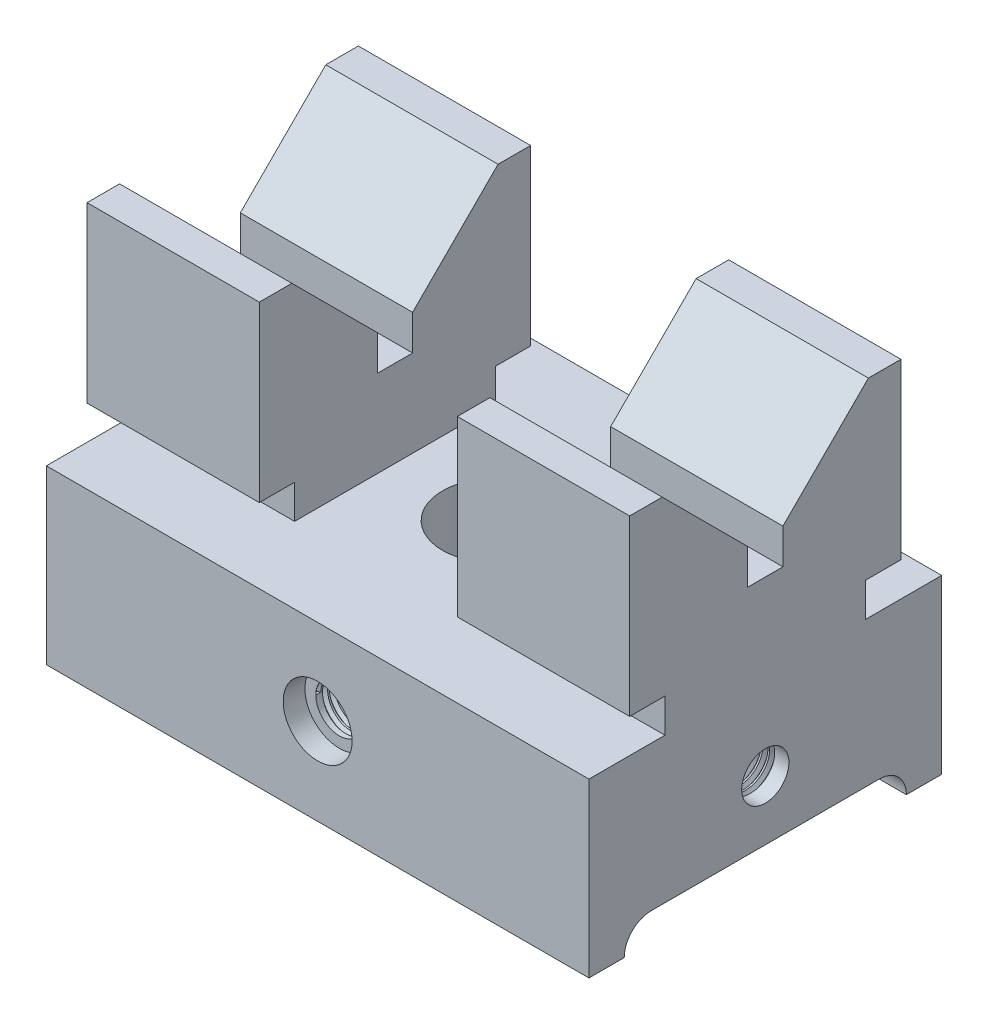
SolidWorks part; units mm, degrees
ref_plane "Front Plane" through (0, 0, 0) normal (0, 0, 1) x (1, 0, 0)
ref_plane "Top Plane" through (0, 0, 0) normal (0, 1, 0) x (1, 0, 0)
ref_plane "Right Plane" through (0, 0, 0) normal (1, 0, 0) x (0, 0, -1)
sketch "Sketch1" plane through (0, 0, 0) normal (1, 0, 0) x (0, 0, -1)
  line L1 (32.5, -35) -> (-32.5, -35)
  line L2 (32.5, -35) -> (32.5, 35)
  line L3 (32.5, 35) -> (-32.5, 35)
  line L4 (-32.5, -35) -> (-32.5, 35)
  line L5 (32.5, -35) -> (-32.5, 35) construction
  line L6 (32.5, 35) -> (-32.5, -35) construction
  point P0 (0, 0)
  dimension "D1" = 65
  dimension "D2" = 70
extrude "Boss-Extrude1" add sketch "Sketch1" along normal mid plane 100
sketch "Sketch3" plane through (50, 0, 0) normal (1, 0, 0) x (0, 0, -1)
  line L0 (0, 35) -> (0, -35) construction
  line L1 (32.5, 35) -> (-32.5, 35) construction
  line L2 (-32.5, -35) -> (32.5, -35) construction
  line L3 (-32.5, -3.25) -> (-18.5, -3.25)
  line L4 (-32.5, 35) -> (-32.5, -35) construction
  line L5 (-18.5, -3.25) -> (-18.5, 3)
  line L6 (-18.5, 3) -> (-25, 3)
  line L7 (-25, 3) -> (-25, 35)
  line L8 (-25, 35) -> (-19, 35)
  line L9 (-19, 35) -> (-3.25, 19.25)
  line L10 (-3.25, 19.25) -> (-3.25, 12.75)
  line L11 (19, 35) -> (3.25, 19.25)
  line L12 (25, 35) -> (19, 35)
  line L13 (25, 3) -> (25, 35)
  line L14 (18.5, 3) -> (25, 3)
  line L15 (18.5, -3.25) -> (18.5, 3)
  line L16 (32.5, -3.25) -> (18.5, -3.25)
  line L17 (-3.25, 12.75) -> (3.25, 12.75)
  line L18 (3.25, 12.75) -> (3.25, 19.25)
  line L19 (32.5, -35) -> (32.5, 35) construction
  line L20 (-26, -35) -> (26, -35)
  line L21 (-26, -35) -> (-26, -30)
  line L22 (-26, -30) -> (26, -30)
  line L23 (26, -35) -> (26, -30)
  point P17 (0, 17.667)
  line M1 (-32.5, 35) -> (-32.5, -35)
  line M3 (32.5, -35) -> (32.5, 35)
  line M4 (32.5, 35) -> (-32.5, 35)
  dimension "D1" = 14
  dimension "D2" = 50
  dimension "D3" = 38
  dimension "D4" = 90
  dimension "D5" = 47.75
  dimension "D6" = 38
  dimension "D7" = 31.75
  dimension "D8" = 6.5
  dimension "D9" = 5
  dimension "D10" = 6.5
  dimension "D11" = 6.5
extrude "Cut-Extrude1" cut sketch "Sketch3" against normal through all contours L16 L13 L14 L15 M3 M4 | L0 L17 L18 L11 M4 | L0 L9 L10 L17 M4 | L6 L7 L3 L5 M4 M1 | L22 L23 L20 L21 region at (50, 27.5863, -5.968) region at (50, 13.8903, -27.8817) region at (50, 13.8903, 27.8817) region at (50, 27.5863, 5.968)
fillet "Fillet1" radius 5 2 edges at (0, -30, 26) (0, -30, -26)
sketch "Sketch4" plane through (50, 0, 0) normal (1, 0, 0) x (0, 0, -1)
  line L0 (-18.5, -3.25) -> (18.5, -3.25)
  line L20 (-32.5, -35) -> (-26, -35)
  line L21 (-21, -30) -> (21, -30)
  line L22 (26, -35) -> (32.5, -35)
  line L23 (32.5, -35) -> (32.5, -3.25)
  line L24 (32.5, -3.25) -> (18.5, -3.25)
  line L25 (18.5, -3.25) -> (18.5, 3)
  line L26 (18.5, 3) -> (25, 3)
  line L27 (25, 3) -> (25, 35)
  line L28 (25, 35) -> (19, 35)
  line L29 (19, 35) -> (3.25, 19.25)
  line L30 (3.25, 19.25) -> (3.25, 12.75)
  line L31 (3.25, 12.75) -> (-3.25, 12.75)
  line L32 (-3.25, 12.75) -> (-3.25, 19.25)
  line L33 (-3.25, 19.25) -> (-19, 35)
  line L34 (-19, 35) -> (-25, 35)
  line L35 (-25, 35) -> (-25, 3)
  line L36 (-25, 3) -> (-18.5, 3)
  line L37 (-18.5, 3) -> (-18.5, -3.25)
  line L38 (-18.5, -3.25) -> (-32.5, -3.25)
  line L39 (-32.5, -3.25) -> (-32.5, -35)
  line L40 (-32.5, -35) -> (-26, -35)
  line L41 (-21, -30) -> (21, -30)
  line L42 (26, -35) -> (32.5, -35)
  line L43 (32.5, -35) -> (32.5, -3.25)
  line L44 (32.5, -3.25) -> (18.5, -3.25)
  line L45 (18.5, -3.25) -> (18.5, 3)
  line L46 (18.5, 3) -> (25, 3)
  line L47 (25, 3) -> (25, 35)
  line L48 (25, 35) -> (19, 35)
  line L49 (19, 35) -> (3.25, 19.25)
  line L50 (3.25, 19.25) -> (3.25, 12.75)
  line L51 (3.25, 12.75) -> (-3.25, 12.75)
  line L52 (-3.25, 12.75) -> (-3.25, 19.25)
  line L53 (-3.25, 19.25) -> (-19, 35)
  line L54 (-19, 35) -> (-25, 35)
  line L55 (-25, 35) -> (-25, 3)
  line L56 (-25, 3) -> (-18.5, 3)
  line L57 (-18.5, 3) -> (-18.5, -3.25)
  line L58 (-18.5, -3.25) -> (-32.5, -3.25)
  line L59 (-32.5, -3.25) -> (-32.5, -35)
  arc A2 (-21, -30) -> (-26, -35) centre (-21, -35) ccw
  arc A3 (26, -35) -> (21, -30) centre (21, -35) ccw
  arc A4 (-21, -30) -> (-26, -35) centre (-21, -35) ccw
  arc A5 (26, -35) -> (21, -30) centre (21, -35) ccw
  line M8 (18.5, -3.25) -> (18.5, 3)
  line M9 (18.5, 3) -> (25, 3)
  line M10 (25, 3) -> (25, 35)
  line M11 (25, 35) -> (19, 35)
  line M12 (19, 35) -> (3.25, 19.25)
  line M13 (3.25, 19.25) -> (3.25, 12.75)
  line M14 (3.25, 12.75) -> (-3.25, 12.75)
  line M15 (-3.25, 12.75) -> (-3.25, 19.25)
  line M16 (-3.25, 19.25) -> (-19, 35)
  line M17 (-19, 35) -> (-25, 35)
  line M18 (-25, 35) -> (-25, 3)
  line M19 (-25, 3) -> (-18.5, 3)
  line M20 (-18.5, 3) -> (-18.5, -3.25)
  dimension "D1" = 0
extrude "Cut-Extrude2" cut sketch "Sketch4" against normal blind 36.5 from offset 31.75 contours L0 M20 M8 M9 M10 M11 M12 M13 M14 M15 M16 M17 M18 M19 region at (50, -0.125, 17.8705) offset against normal yes
sketch "Sketch5" plane through (0, -3.25, 0) normal (0, 1, 0) x (1, 0, 0)
  circle A0 centre (0, 0) radius 9.5
  dimension "D1" = 19
extrude "Cut-Extrude3" cut sketch "Sketch5" against normal through all
hole_wizard "CBORE for M10 Hex Head Machine Screw1" positions "Sketch6" profile "Sketch7" counterbore size "M10" standard "ANSI Metric"
sketch "Sketch6" plane through (0, 0, 32.5) normal (0, 0, 1) x (1, 0, 0)
  line L0 (-50, -3.25) -> (-50, -35) construction
  line L1 (50, -35) -> (-50, -35) construction
  point P0 (0, -19)
  dimension "D1" = 50
  dimension "D2" = 16
sketch "Sketch7" plane through (0, -19, 32.5) normal (1, 0, 0) x (0, -1, 0)
  line L0 (0, 0) -> (0, 22.6137)
  line L1 (0, 22.6137) -> (4.35, 20)
  line L2 (4.35, 20) -> (4.35, 4)
  line L3 (4.35, 4) -> (6.35, 4)
  line L4 (6.35, 4) -> (6.35, 0)
  line L5 (6.35, 0) -> (0, 0)
  line L10 (0, 22.6137) -> (-4.35, 20) construction
  line L11 (0, -6.35) -> (0, 107.95) construction
  dimension "Hole Dia." = 8.7
  dimension "Hole Depth" = 20
  dimension "C'Bore Dia." = 12.7
  dimension "C'Bore Depth" = 4
  dimension "Drill Angle" = 118
thread "Thread1" pitch 1.25 method cut profile "Thread Profile1" start angle 0, offset 0, length 10, pitch 1.25, diameter 8.7
ref_plane "Plane1" through (-4.35, -19, 28.5) normal (0, -1, 0) x (-1, 0, 0)
sketch "Thread Profile1" plane through (-4.35, -19, 28.5) normal (0, -1, 0) x (-1, 0, 0)
  line L0 (0, 0) -> (0, 1.25) construction
  line L1 (0, 0) -> (0.6766, 0.3906)
  line L2 (0.6766, 0.3906) -> (0.6766, 0.5469)
  line L3 (0.6766, 0.5469) -> (0, 0.9375)
  line L4 (0.6766, 0.4687) -> (0, 0.4687) construction
  line L11 (0, 0) -> (0, 0.9375)
  point P2 (0, 0)
  dimension "Pitch" = 1.25
  dimension "Profile_Angle" = 60
  dimension "Profile_Land" = 0.1562
  dimension "Profile_Height" = 0.6766
hole_wizard "Ø8.7 (8.7) Diameter Hole1" positions "Sketch12" profile "Sketch13" hole size "Ø8.7" standard "ANSI Metric"
sketch "Sketch12" plane through (50, 0, 0) normal (1, 0, 0) x (0, 0, -1)
  line L0 (-32.5, -3.25) -> (-32.5, -35) construction
  line L1 (-32.5, -35) -> (-26, -35) construction
  point P0 (0, -19)
  dimension "D1" = 32.5
  dimension "D2" = 16
sketch "Sketch13" plane through (50, -19, 0) normal (0, 1, 0) x (0, 0, -1)
  line L0 (0, 0) -> (0, 18.6137)
  line L1 (0, 18.6137) -> (4.35, 16)
  line L2 (4.35, 16) -> (4.35, 0)
  line L5 (4.35, 0) -> (0, 0)
  line L10 (0, 18.6137) -> (-4.35, 16) construction
  line L11 (0, -6.35) -> (0, 107.95) construction
  dimension "Hole Dia." = 8.7
  dimension "Hole Depth" = 16
  dimension "Drill Angle" = 118
thread "Thread2" pitch 1.25 method cut profile "Thread Profile2" start angle 0, offset 2, length 16, pitch 1.25, diameter 8.7
ref_plane "Plane2" through (48, -19, 4.35) normal (0, -1, 0) x (0, 0, 1)
sketch "Thread Profile2" plane through (48, -19, 4.35) normal (0, -1, 0) x (0, 0, 1)
  line L0 (0, 0) -> (0, 1.25) construction
  line L1 (0, 0) -> (0.6766, 0.3906)
  line L2 (0.6766, 0.3906) -> (0.6766, 0.5469)
  line L3 (0.6766, 0.5469) -> (0, 0.9375)
  line L4 (0.6766, 0.4687) -> (0, 0.4687) construction
  line L11 (0, 0) -> (0, 0.9375)
  point P2 (0, 0)
  dimension "Pitch" = 1.25
  dimension "Profile_Angle" = 60
  dimension "Profile_Land" = 0.1562
  dimension "Profile_Height" = 0.6766
